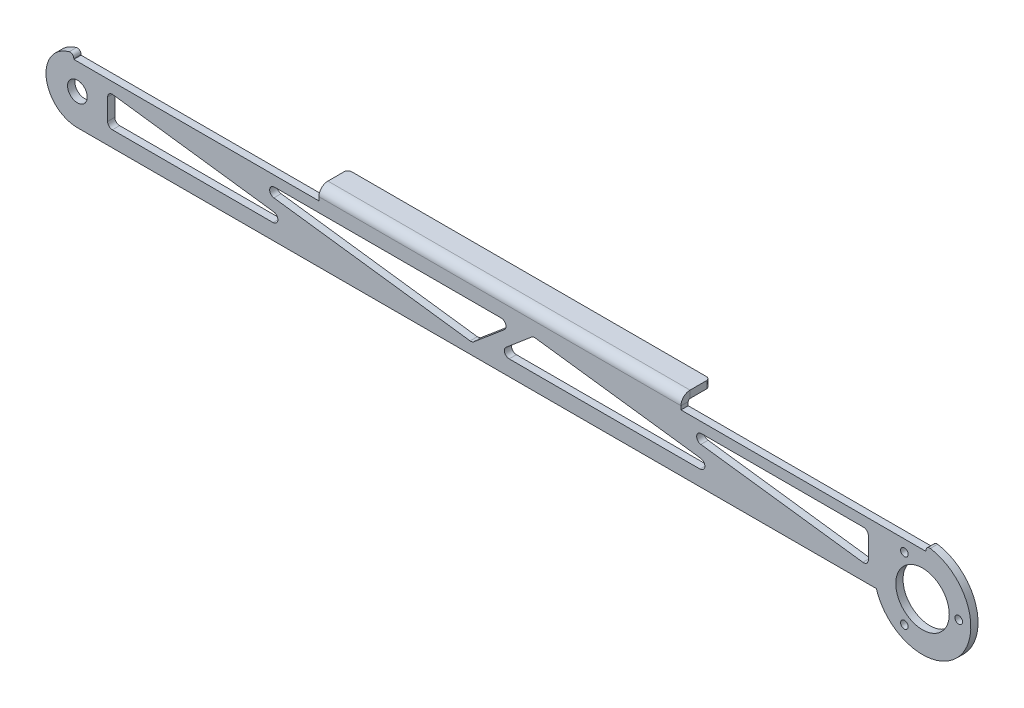
SolidWorks part; units mm, degrees
note: The reader was unsure of these and kept them because the rebuilt part matched: flange length of "Edge-Flange2".
material "6061 Alloy"
ref_plane "Front Plane" through (0, 0, 0) normal (0, 0, 1) x (1, 0, 0)
ref_plane "Top Plane" through (0, 0, 0) normal (0, 1, 0) x (1, 0, 0)
ref_plane "Right Plane" through (0, 0, 0) normal (1, 0, 0) x (0, 0, -1)
sketch "Sketch1" plane through (0, 0, 0) normal (0, 0, 1) x (1, 0, 0)
  line L0 (0, 13) -> (349.93, 13)
  line L1 (55, 0) -> (-55, 0) construction
  line L4 (0, -13) -> (330.8054, -12.8524)
  arc A0 (0, 13) -> (0, -13) centre (0, 0) ccw
  arc A2 (0, -13) -> (0, 13) centre (0, 0) ccw construction
  arc A3 (330.8054, -12.8524) -> (349.93, 13) centre (349.93, -7) ccw
  arc A4 (349.93, 13) -> (330.8054, -12.8524) centre (349.93, -7) ccw construction
  dimension "D1" = 26
  dimension "D2" = 40
  dimension "D3" = 349.93
base flange "Base-Flange1" sketch "Sketch1" thickness 3 reverse thickness direction no parameters "D1"=0.7366
edge flange "Edge-Flange2" sketch "Sketch21" flange angle 90 flange length 12 flange position material outside bend radius 0.7366 thickness 3 relief rectangular parameters "D6"=10
sketch "Sketch21" plane through (0, 13, -3) normal (0, -1, 0) x (-1, 0, 0)
  line L2 (-349.93, 0) -> (-349.93, 9)
  line L3 (-349.93, 9) -> (0, 9)
  line L4 (0, 9) -> (0, 0)
  line L8 (0, 0) -> (-349.93, 0) construction
  line L9 (0, 0) -> (-349.93, 0)
bend "EdgeBend2" bend radius 0.7366 bend angle 90 parameters "D5"=1
sketch "Sketch22" plane through (0, 0, 0) normal (0, 0, 1) x (1, 0, 0)
  circle A0 centre (0, 0) radius 4.075
  circle A1 centre (349.93, -7) radius 11.075
  circle A2 centre (364.93, -7) radius 1.575
  circle A3 centre (342.43, 5.9904) radius 1.575
  circle A4 centre (342.43, -19.9904) radius 1.575
  dimension "D1" = 8.15
  dimension "D2" = 22.15
  dimension "D3" = 3.15
  dimension "D4" = 15
  dimension "D5" = 3
extrude "Cut-Extrude1" cut sketch "Sketch22" against normal through all both and the other way through all normal cut yes
sketch "Sketch23" plane through (0, 0, 0) normal (0, 0, 1) x (1, 0, 0)
  line L0 (12.5, 6.5) -> (12.5, -6.5)
  line L3 (327.5, 6.5) -> (227.5, 6.5)
  line L5 (50.9615, 6.5) -> (163.4781, -8.2523)
  line L6 (50.9615, 6.5) -> (12.5, 6.5) construction
  line L7 (349.93, 12.2634) -> (0, 12.2634) construction
  line L8 (12.5, 6.5) -> (111.6514, -6.5)
  line L9 (12.5, -6.5) -> (111.6514, -6.5)
  line L10 (173.3081, -6.5) -> (288.7148, -6.5)
  line L11 (180.9615, 6.5) -> (163.4781, -8.2523)
  line L12 (173.3081, -6.5) -> (188.7148, 6.5)
  line L13 (188.7148, 6.5) -> (288.7148, -6.5)
  line L14 (227.5, 6.5) -> (327.5, -6.5)
  line L15 (227.5, 6.5) -> (188.7148, 6.5) construction
  line L16 (180.9615, 6.5) -> (50.9615, 6.5)
  line L19 (188.7148, 6.5) -> (180.9615, 6.5) construction
  line L20 (327.5, 6.5) -> (327.5, -6.5)
  point P2 (12.5, 0)
  dimension "D1" = 12.5
  dimension "D2" = 315
  dimension "D3" = 13
  dimension "D4" = 100
  dimension "D5" = 5
  dimension "D6" = 5
  dimension "D7" = 100
  dimension "D8" = 5
  dimension "D9" = 130
extrude "Cut-Extrude2" cut sketch "Sketch23" against normal through all both and the other way through all normal cut yes
fillet "Fillet1" radius 2 14 edges at (12.5, 6.5, -1.5) (173.3081, -6.5, -1.5) (188.7148, 6.5, -1.5) (163.4781, -8.2523, -1.5) (180.9615, 6.5, -1.5) (0, 14.5, -12) (349.93, 14.5, -12) (327.5, -6.5, -1.5) (327.5, 6.5, -1.5) (12.5, -6.5, -1.5)
sketch "Sketch24" plane through (0, 0, 0) normal (0, 0, 1) x (1, 0, 0)
  line L0 (0, 16) -> (349.93, 16) construction
  line L1 (0, 10.7634) -> (100, 10.7634)
  line L2 (0, 10.7634) -> (0, 16)
  line L3 (0, 16) -> (100, 16)
  line L4 (100, 10.7634) -> (100, 16)
  line L5 (0, 10.7634) -> (100, 16) construction
  line L6 (0, 16) -> (100, 10.7634) construction
  line L8 (349.93, 10.7634) -> (249.93, 10.7634)
  line L9 (349.93, 10.7634) -> (349.93, 16)
  line L10 (349.93, 16) -> (249.93, 16)
  line L11 (249.93, 10.7634) -> (249.93, 16)
  line L12 (349.93, 10.7634) -> (249.93, 16) construction
  line L13 (349.93, 16) -> (249.93, 10.7634) construction
  point P4 (50, 13.3817)
  point P12 (299.93, 13.3817)
  dimension "D1" = 100
  dimension "D2" = 100
extrude "Cut-Extrude3" cut sketch "Sketch24" against normal through all both and the other way through all normal cut yes
fillet "Fillet2" radius 1.5 4 edges at (-1.5, 12.9132, -1.5) (351.43, 12.9437, -1.5) (249.93, 14.5, -12) (100, 14.5, -12)
sketch "Bend-Lines1" plane through (0, 0, 0) normal (0, 1, 0) x (1, 0, 0)
sketch "Bounding-Box1" plane through (0, 0, 0) normal (0, 1, 0) x (1, 0, 0)
sheet metal parameters "Sheet-Metal1" thickness 3 parameters "D1"=0.7366
flat pattern "Flat-Pattern1"
sketch "Bend-Lines2" plane through (0, 0, 0) normal (0, 1, 0) x (1, 0, 0)
sketch3d "Bounding-Box2"
  line L0 (-361.91, 34.4982, 0) -> (20.7837, 19.1843, 0) construction
  line L1 (-363.5094, -5.4698, 0) -> (19.1843, -20.7837, 0) construction
  line L2 (-361.91, 34.4982, 0) -> (-363.5094, -5.4698, 0) construction
  line L3 (20.7837, 19.1843, 0) -> (19.1843, -20.7837, 0) construction
sheet metal parameters "Sheet-Metal3" thickness 3 parameters "D1"=0.7366
flat pattern "Flat-Pattern1"
sketch "Bend-Lines2" plane through (0, 0, 0) normal (0, 0, 1) x (1, 0, 0)
  line L0 (350, 14.75) -> (0, 14.75) construction
  line L1 (350, 14.75) -> (0, 14.75) construction
sketch3d "Bounding-Box2"
  line L0 (-361.6909, 39.9734, 0) -> (21.0028, 24.6596, 0) construction
  line L1 (-363.5094, -5.4698, 0) -> (19.1843, -20.7837, 0) construction
  line L2 (-361.6909, 39.9734, 0) -> (-363.5094, -5.4698, 0) construction
  line L3 (21.0028, 24.6596, 0) -> (19.1843, -20.7837, 0) construction
bend of the flat pattern "Flatten-<EdgeBend2>1"
sheet metal parameters "Sheet-Metal4" thickness 3 parameters "D1"=0.7366
flat pattern "Flat-Pattern1"
sketch "Bend-Lines2" plane through (0, 0, 0) normal (0, 0, 1) x (1, 0, 0)
  line L0 (349.93, 14.75) -> (0, 14.75) construction
  line L1 (349.93, 14.75) -> (0, 14.75) construction
sketch3d "Bounding-Box2"
  line L0 (-361.6207, 39.9735, 0) -> (21.003, 24.6594, 0) construction
  line L1 (-363.4395, -5.4697, 0) -> (19.1842, -20.7838, 0) construction
  line L2 (-361.6207, 39.9735, 0) -> (-363.4395, -5.4697, 0) construction
  line L3 (21.003, 24.6594, 0) -> (19.1842, -20.7838, 0) construction
bend of the flat pattern "Flatten-<EdgeBend2>1"
sheet metal parameters "Sheet-Metal5" thickness 3 parameters "D1"=0.7366
flat pattern "Flat-Pattern1"
sketch "Bend-Lines2" plane through (0, 0, 0) normal (0, 0, 1) x (1, 0, 0)
  line L0 (349.93, 14.75) -> (0, 14.75) construction
  line L1 (349.93, 14.75) -> (0, 14.75) construction
sketch3d "Bounding-Box2"
  line L0 (-361.3441, 46.8836, 0) -> (21.2795, 31.5695, 0) construction
  line L1 (-363.4395, -5.4697, 0) -> (19.1842, -20.7838, 0) construction
  line L2 (-361.3441, 46.8836, 0) -> (-363.4395, -5.4697, 0) construction
  line L3 (21.2795, 31.5695, 0) -> (19.1842, -20.7838, 0) construction
bend of the flat pattern "Flatten-<EdgeBend2>1"
sheet metal parameters "Sheet-Metal6" thickness 3 parameters "D1"=0.7366
flat pattern "Flat-Pattern1"
sketch "Bend-Lines2" plane through (0, 0, 0) normal (0, 0, 1) x (1, 0, 0)
  line L0 (249.93, 14.75) -> (100, 14.75) construction
  line L1 (249.93, 14.75) -> (100, 14.75) construction
sketch3d "Bounding-Box2"
  line L0 (-361.5032, 42.9076, 0) -> (21.1204, 27.5934, 0) construction
  line L1 (-363.4395, -5.4697, 0) -> (19.1842, -20.7838, 0) construction
  line L2 (-361.5032, 42.9076, 0) -> (-363.4395, -5.4697, 0) construction
  line L3 (21.1204, 27.5934, 0) -> (19.1842, -20.7838, 0) construction
bend of the flat pattern "Flatten-<EdgeBend2>1"
